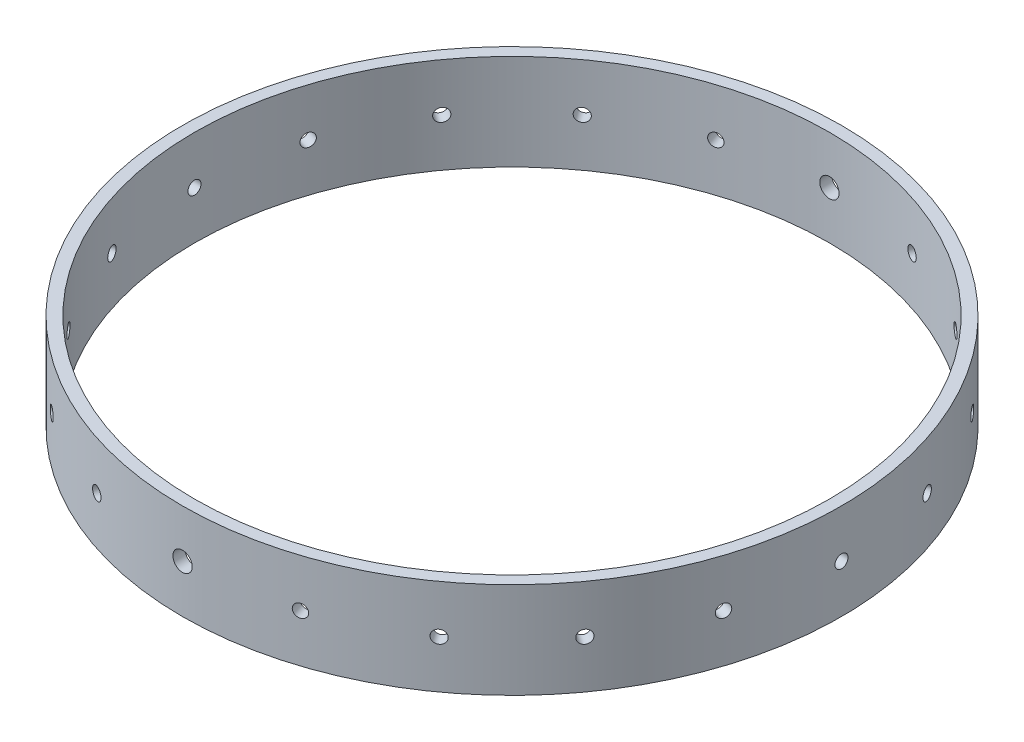
SolidWorks part; units mm, degrees
ref_plane "Front Plane" through (0, 0, 0) normal (0, 0, 1) x (1, 0, 0)
ref_plane "Top Plane" through (0, 0, 0) normal (0, 1, 0) x (1, 0, 0)
ref_plane "Right Plane" through (0, 0, 0) normal (1, 0, 0) x (0, 0, -1)
sketch "Sketch1" plane through (0, 0, 0) normal (0, 1, 0) x (1, 0, 0)
  circle A0 centre (0, 0) radius 87.3125
  circle A1 centre (0, 0) radius 84.1375
  dimension "D1" = 174.625
  dimension "D2" = 168.275
extrude "Boss-Extrude1" add sketch "Sketch1" along normal blind 25.4
ref_plane "Plane1" through (0, 0, 87.3125) normal (0, 0, 1) x (1, 0, 0)
sketch "Sketch4" plane through (0, 0, 87.3125) normal (0, 0, 1) x (1, 0, 0)
  line L0 (0, 25.4) -> (0, 12.7)
  line L1 (87.3125, 25.4) -> (-87.3125, 25.4) construction
hole_wizard "1/4-20 Tapped Hole1" positions "Sketch5" profile "Sketch6" tap size "1/4-20" standard "ANSI Inch"
sketch "Sketch5" plane through (0, 0, 87.3125) normal (0, 0, 1) x (1, 0, 0)
  point P0 (0, 12.7)
sketch "Sketch6" plane through (0, 12.7, 87.3125) normal (1, 0, 0) x (0, -1, 0)
  line L0 (0, 0) -> (0, 14.2338)
  line L1 (0, 14.2338) -> (2.5527, 12.7)
  line L2 (2.5527, 12.7) -> (2.5527, 0)
  line L5 (2.5527, 0) -> (0, 0)
  line L10 (0, 14.2338) -> (-2.5527, 12.7) construction
  line L11 (0, -6.35) -> (0, 107.95) construction
  dimension "Tap Drill Dia." = 5.1054
  dimension "Tap Drill Depth" = 12.7
  dimension "Drill Angle" = 118
cosmetic thread "Hole Thread1" parameters "D1"=3.2137, "D2"=6.35
ref_plane "Plane3" through (87.3125, 0, 0) normal (1, 0, 0) x (0, 0, -1)
sketch "Sketch7" plane through (87.3125, 0, 0) normal (1, 0, 0) x (0, 0, -1)
  line L0 (0, 25.4) -> (0, 12.7)
  line L1 (87.3125, 25.4) -> (-87.3125, 25.4) construction
hole_wizard "#8-32 Tapped Hole1" positions "Sketch8" profile "Sketch9" tap size "#8-32" standard "ANSI Inch"
sketch "Sketch8" plane through (87.3125, 0, 0) normal (1, 0, 0) x (0, 0, -1)
  point P0 (0, 12.7)
sketch "Sketch9" plane through (87.3125, 12.7, 0) normal (0, 1, 0) x (0, 0, -1)
  line L0 (0, 0) -> (0, 13.7378)
  line L1 (0, 13.7378) -> (1.7272, 12.7)
  line L2 (1.7272, 12.7) -> (1.7272, 0)
  line L5 (1.7272, 0) -> (0, 0)
  line L10 (0, 13.7378) -> (-1.7272, 12.7) construction
  line L11 (0, -6.35) -> (0, 107.95) construction
  dimension "Tap Drill Dia." = 3.4544
  dimension "Tap Drill Depth" = 12.7
  dimension "Drill Angle" = 118
cosmetic thread "Hole Thread2" parameters "D1"=3.1927, "D2"=4.1656
sketch "Sketch2" plane through (0, 0, 87.3125) normal (0, 0, 1) x (1, 0, 0)
  line L0 (84.1375, 25.4) -> (-84.1375, 25.4) construction
  circle A0 centre (0, 12.7) radius 1.5875
  dimension "D1" = 3.175
  dimension "D2" = 12.7
ref_axis "Axis1" through (0, 25.4, 0) along (0, -1, 0)
ref_plane "Plane2" through (0, 0, 84.1375) normal (0, 0, 1) x (1, 0, 0)
pattern_circular "CirPattern1" count 2 over 360 about axis through (0, 25.4, 0) along (0, -1, 0) of "1/4-20 Tapped Hole1"
pattern_circular "CirPattern2" count 20 over 360 about axis through (0, 25.4, 0) along (0, -1, 0) skipping 5, 15 of "#8-32 Tapped Hole1"
